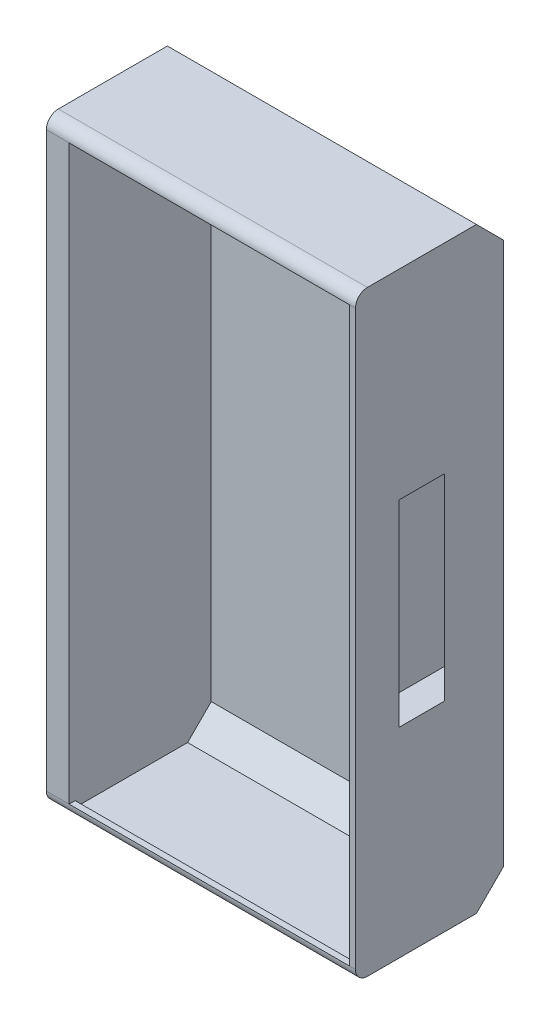
SolidWorks part; units mm, degrees
ref_plane "Front Plane" through (0, 0, 0) normal (1, 0, 0) x (0, 1, 0)
ref_plane "Top Plane" through (0, 0, 0) normal (0, 0, 1) x (0, 1, 0)
ref_plane "Right Plane" through (0, 0, 0) normal (0, 1, 0) x (-1, 0, 0)
sketch "Sketch1" plane through (0, 0, 0) normal (1, 0, 0) x (0, 1, 0)
  line L12 (-98.46, -42.4834) -> (-89.4834, -51.46)
  line L13 (-89.4834, -51.46) -> (89.4834, -51.46)
  line L14 (89.4834, -51.46) -> (98.46, -42.4834)
  line L15 (98.46, -42.4834) -> (98.46, -6.5)
  line L16 (94.5, -2.54) -> (-94.5, -2.54)
  line L17 (-98.46, -6.5) -> (-98.46, -42.4834)
  line L18 (-98.46, -42.4834) -> (-89.4834, -51.46)
  line L19 (-89.4834, -51.46) -> (89.4834, -51.46)
  line L20 (89.4834, -51.46) -> (98.46, -42.4834)
  line L21 (98.46, -42.4834) -> (98.46, -6.5)
  line L22 (94.5, -2.54) -> (-94.5, -2.54)
  line L23 (-98.46, -6.5) -> (-98.46, -42.4834)
  arc A4 (98.46, -6.5) -> (94.5, -2.54) centre (94.5, -6.5) ccw
  arc A5 (-94.5, -2.54) -> (-98.46, -6.5) centre (-94.5, -6.5) ccw
  arc A6 (98.46, -6.5) -> (94.5, -2.54) centre (94.5, -6.5) ccw
  arc A7 (-94.5, -2.54) -> (-98.46, -6.5) centre (-94.5, -6.5) ccw
  dimension "D1" = 0.04
extrude "Boss-Extrude1" add sketch "Sketch1" along normal up to surface (102 mm away) contours L18 L19 L20 L21 A6 L22 A7 L23
ref_plane "Plane3" through (0, 0, 0) normal (0, 1, 0) x (1, 0, 0)
sketch "Sketch11" plane through (0, 0, 0) normal (0, 1, 0) x (1, 0, 0)
  line L0 (102, 24.4917) -> (104.8284, 21.6633)
  line L1 (102, 6.5) -> (102, 42.4834) construction
  line L2 (102, 24.4917) -> (92.1005, 34.3912)
  dimension "D1" = 14
  dimension "D2" = 4
  dimension "D3" = 45
sketch "Sketch12" plane through (102, 0, 0) normal (1, 0, 0) x (0, 1, 0)
  line L0 (0, -24.4917) -> (0, -21.6633) construction
  line L1 (-32.5, -31.9917) -> (32.5, -31.9917)
  line L2 (-32.5, -31.9917) -> (-32.5, -16.9917)
  line L3 (-32.5, -16.9917) -> (32.5, -16.9917)
  line L4 (32.5, -31.9917) -> (32.5, -16.9917)
  line L5 (-32.5, -31.9917) -> (32.5, -16.9917) construction
  line L6 (-32.5, -16.9917) -> (32.5, -31.9917) construction
  line L7 (0, -24.4917) -> (0, -34.3912) construction
  line L10 (89.4834, -51.46) -> (-89.4834, -51.46) construction
  point P0 (0, -24.4917)
  dimension "D1" = 65
  dimension "D2" = 15
  dimension "D3" = 26.9683
sweep "Cut-Sweep1" cut profiles "Sketch12" path "Sketch11"
shell "Shell1" thickness 2 removed face at (51, 0, -2.54)
sketch "Sketch8" plane through (2, 0, 0) normal (1, 0, 0) x (0, 1, 0)
  line L11 (-10, -27) -> (-10, -17)
  line L12 (-10, -17) -> (10, -17)
  line L13 (10, -27) -> (10, -17)
  line L15 (-98.46, -42.4834) -> (-89.4834, -51.46)
  line L16 (-89.4834, -51.46) -> (89.4834, -51.46)
  line L17 (89.4834, -51.46) -> (98.46, -42.4834)
  line L18 (98.46, -42.4834) -> (98.46, -6.5)
  line L19 (94.5, -2.54) -> (-94.5, -2.54)
  line L20 (-98.46, -6.5) -> (-98.46, -42.4834)
  line L21 (-98.46, -42.4834) -> (-89.4834, -51.46)
  line L22 (-89.4834, -51.46) -> (89.4834, -51.46)
  line L23 (89.4834, -51.46) -> (98.46, -42.4834)
  line L24 (98.46, -42.4834) -> (98.46, -6.5)
  line L25 (94.5, -2.54) -> (-94.5, -2.54)
  line L26 (-98.46, -6.5) -> (-98.46, -42.4834)
  arc A0 (-10, -27) -> (10, -27) centre (0, -27) ccw
  arc A5 (98.46, -6.5) -> (94.5, -2.54) centre (94.5, -6.5) ccw
  arc A6 (-94.5, -2.54) -> (-98.46, -6.5) centre (-94.5, -6.5) ccw
  arc A7 (98.46, -6.5) -> (94.5, -2.54) centre (94.5, -6.5) ccw
  arc A8 (-94.5, -2.54) -> (-98.46, -6.5) centre (-94.5, -6.5) ccw
  point P4 (0, -51.46)
  dimension "D2" = 20
  dimension "D3" = 24.46
  dimension "D4" = 10
  dimension "D5" = 20
  dimension "D1" = 0
extrude "Boss-Extrude2" add sketch "Sketch8" along normal blind 5.5 contours L26 L21 L22 L23 L24 A7 L25 A8
extrude "Cut-Extrude1" cut sketch "Sketch8<6>" along normal blind 3.1 and the other way blind 1 contours L11 A0 L13 L12 region at (2, 0, -26.0665)
sketch "Sketch8<6>" plane through (2, 0, 0) normal (1, 0, 0) x (0, 1, 0) same geometry as "Sketch8"
pattern_linear "LPattern3" count 2 spacing 22 along (0, 1, 0) count 2 spacing 22 along (0, -1, 0) of "Cut-Extrude1" pattern seed only yes
chamfer "Chamfer1" distance 20 angle 45 1 edges at (100, 0, -36.8201) first distance on face at (100, 0, -20.8578)
sketch "Sketch13" plane through (7.5, 0, 0) normal (1, 0, 0) x (0, 1, 0)
  line L3 (-96.46, -6.5) -> (-94.5, -4.54)
  line L4 (0, -55.1052) -> (0, 55.1052) construction
  line L5 (96.46, -6.5) -> (94.5, -4.54)
  arc A1 (-94.5, -4.54) -> (-96.46, -6.5) centre (-94.5, -6.5) ccw
  arc A2 (94.5, -4.54) -> (96.46, -6.5) centre (94.5, -6.5) cw
  arc A3 (-94.5, -4.54) -> (-96.46, -6.5) centre (-94.5, -6.5) ccw construction
  point P11 (-96.46, -6.5)
  point P13 (-94.5, -4.54)
  point P15 (0, 0)
  point P16 (0, 0)
extrude "Boss-Extrude4" add sketch "Sketch13" along normal up to surface (92.5 mm away) up to face at (100, 0, -24.2732)
